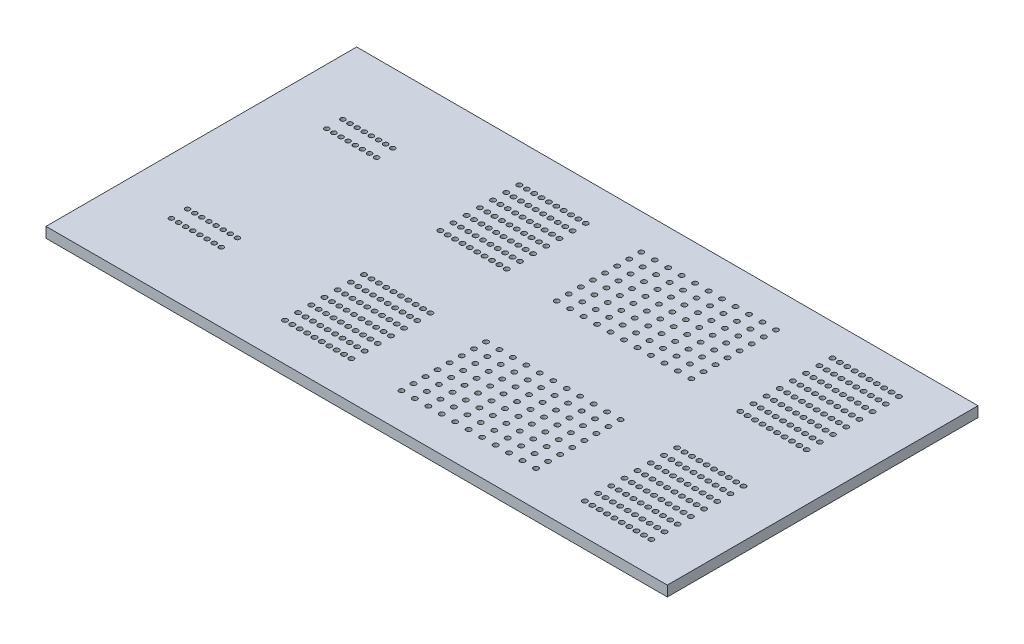
SolidWorks part; units mm, degrees
ref_plane "Plan de face" through (0, 0, 0) normal (0, 0, 1) x (1, 0, 0)
ref_plane "Plan de dessus" through (0, 0, 0) normal (0, 1, 0) x (1, 0, 0)
ref_plane "Plan de droite" through (0, 0, 0) normal (1, 0, 0) x (0, 0, -1)
sketch "Esquisse2" plane through (0, 0, 0) normal (0, 1, 0) x (1, 0, 0)
  line L1 (-60, -15) -> (60, -15)
  line L2 (-60, -15) -> (-60, 15)
  line L3 (-60, 15) -> (60, 15)
  line L4 (60, -15) -> (60, 15)
  line L5 (-60, -15) -> (60, 15) construction
  line L6 (-60, 15) -> (60, -15) construction
  point P0 (0, 0)
  dimension "D1" = 30
  dimension "D2" = 120
extrude "Boss.-Extru.1" add sketch "Esquisse2" along normal blind 2 contours L3 L4 L1 L2
sketch "Cavités" plane through (0, 0, 0) normal (0, 1, 0) x (1, 0, 0)
  line L0 (-60, -15) -> (60, -15) construction
  line L1 (-58.4, 15) -> (-30.4, 15) construction
  line L2 (-58.4, 15) -> (-58.4, -15) construction
  line L3 (-58.4, -15) -> (-30.4, -15) construction
  line L4 (-30.4, 15) -> (-30.4, -15) construction
  line L5 (-60, 15) -> (60, 15) construction
  line L6 (-28.8, 15) -> (-0.8, 15) construction
  line L7 (-28.8, 15) -> (-28.8, -15) construction
  line L8 (-28.8, -15) -> (-0.8, -15) construction
  line L9 (-0.8, 15) -> (-0.8, -15) construction
  line L10 (-30.4, 15) -> (-28.8, 15) construction
  line L11 (0.8, 15) -> (28.8, 15) construction
  line L12 (0.8, 15) -> (0.8, -15) construction
  line L13 (0.8, -15) -> (28.8, -15) construction
  line L14 (28.8, 15) -> (28.8, -15) construction
  line L15 (30.4, 15) -> (58.4, 15) construction
  line L16 (30.4, 15) -> (30.4, -15) construction
  line L17 (30.4, -15) -> (58.4, -15) construction
  line L18 (58.4, 15) -> (58.4, -15) construction
  line L19 (-0.8, 15) -> (0.8, 15) construction
  line L20 (28.8, 15) -> (30.4, 15) construction
  line L21 (-60, 15) -> (-58.4, 15) construction
  line L22 (58.4, 15) -> (60, 15) construction
  dimension "D1" = 28
  dimension "D2" = 1.6
sketch "Esquisse7" plane through (0, 2, 0) normal (0, 1, 0) x (1, 0, 0)
  line L0 (-58.4, 0) -> (-49.2195, 0) construction
  line L1 (-49.2195, 1.5555) -> (-39.5805, 1.5555) construction
  line L2 (-49.2195, 1.5555) -> (-49.2195, -1.5555) construction
  line L3 (-49.2195, -1.5555) -> (-39.5805, -1.5555) construction
  line L4 (-39.5805, 1.5555) -> (-39.5805, -1.5555) construction
  line L5 (-58.4, 15) -> (-58.4, -15) construction
  line L6 (-39.5805, 0) -> (-30.4, 0) construction
  line L7 (-30.4, 15) -> (-30.4, -15) construction
  dimension "D1" = 9.639
  dimension "D2" = 3.111
sketch "Esquisse8" plane through (0, 2, 0) normal (0, 1, 0) x (1, 0, 0)
  circle A0 centre (-49.2195, 1.5555) radius 0.45
  dimension "D1" = 0.9
extrude "Enlèv. mat.-Extru.3" cut sketch "Esquisse8" against normal up to next
pattern_linear "Répétition linéaire4" count 8 spacing 1.377 along (1, 0, 0) count 2 spacing 3.111 along (0, 0, 1) of "Enlèv. mat.-Extru.3"
sketch "Esquisse9" plane through (0, 2, 0) normal (0, 1, 0) x (1, 0, 0)
  line L0 (-28.8, 0) -> (-21.2125, 0) construction
  line L1 (-21.2125, 7.635) -> (-8.3875, 7.635) construction
  line L2 (-21.2125, 7.635) -> (-21.2125, -7.635) construction
  line L3 (-21.2125, -7.635) -> (-8.3875, -7.635) construction
  line L4 (-8.3875, 7.635) -> (-8.3875, -7.635) construction
  line L5 (-28.8, 15) -> (-28.8, -15) construction
  line L6 (-8.3875, 0) -> (-0.8, 0) construction
  line L7 (-0.8, 15) -> (-0.8, -15) construction
  dimension "D1" = 12.825
  dimension "D2" = 15.27
sketch "Esquisse10" plane through (0, 2, 0) normal (0, 1, 0) x (1, 0, 0)
  circle A0 centre (-21.2125, 7.635) radius 0.475
  dimension "D1" = 0.95
extrude "Enlèv. mat.-Extru.4" cut sketch "Esquisse10" against normal up to next
pattern_linear "Répétition linéaire5" count 10 spacing 1.425 along (1, 0, 0) count 7 spacing 2.545 along (0, 0, 1) of "Enlèv. mat.-Extru.4"
sketch "Esquisse11" plane through (0, 2, 0) normal (0, 1, 0) x (1, 0, 0)
  line L0 (0.8, 0) -> (1.8, 0) construction
  line L1 (1.8, 8.1655) -> (27.8, 8.1655) construction
  line L2 (1.8, 8.1655) -> (1.8, -8.1655) construction
  line L3 (1.8, -8.1655) -> (27.8, -8.1655) construction
  line L4 (27.8, 8.1655) -> (27.8, -8.1655) construction
  line L5 (0.8, 15) -> (0.8, -15) construction
  line L6 (27.8, 0) -> (28.8, 0) construction
  line L7 (28.8, 15) -> (28.8, -15) construction
  dimension "D1" = 26
  dimension "D2" = 16.331
sketch "Esquisse12" plane through (0, 2, 0) normal (0, 1, 0) x (1, 0, 0)
  circle A0 centre (1.8, 8.1655) radius 0.475
  dimension "D1" = 0.95
extrude "Enlèv. mat.-Extru.5" cut sketch "Esquisse12" against normal up to next
pattern_linear "Répétition linéaire6" count 11 spacing 2.6 along (1, 0, 0) count 8 spacing 2.333 along (0, 0, 1) of "Enlèv. mat.-Extru.5"
sketch "Esquisse13" plane through (0, 2, 0) normal (0, 1, 0) x (1, 0, 0)
  line L0 (30.4, 0) -> (37.9875, 0) construction
  line L1 (37.9875, 8.9075) -> (50.8125, 8.9075) construction
  line L2 (37.9875, 8.9075) -> (37.9875, -8.9075) construction
  line L3 (37.9875, -8.9075) -> (50.8125, -8.9075) construction
  line L4 (50.8125, 8.9075) -> (50.8125, -8.9075) construction
  line L5 (30.4, 15) -> (30.4, -15) construction
  line L6 (50.8125, 0) -> (58.4, 0) construction
  line L7 (58.4, 15) -> (58.4, -15) construction
  dimension "D1" = 17.815
  dimension "D2" = 12.825
sketch "Esquisse14" plane through (0, 2, 0) normal (0, 1, 0) x (1, 0, 0)
  circle A0 centre (37.9875, 8.9075) radius 0.475
  dimension "D1" = 0.95
extrude "Enlèv. mat.-Extru.6" cut sketch "Esquisse14" against normal up to next
pattern_linear "Répétition linéaire7" count 10 spacing 1.425 along (1, 0, 0) count 8 spacing 2.545 along (0, 0, 1) of "Enlèv. mat.-Extru.6"
mirror "Symétrie1" about plane through (-60, 2, 15) normal (0, 0, -1) of bodies 114
